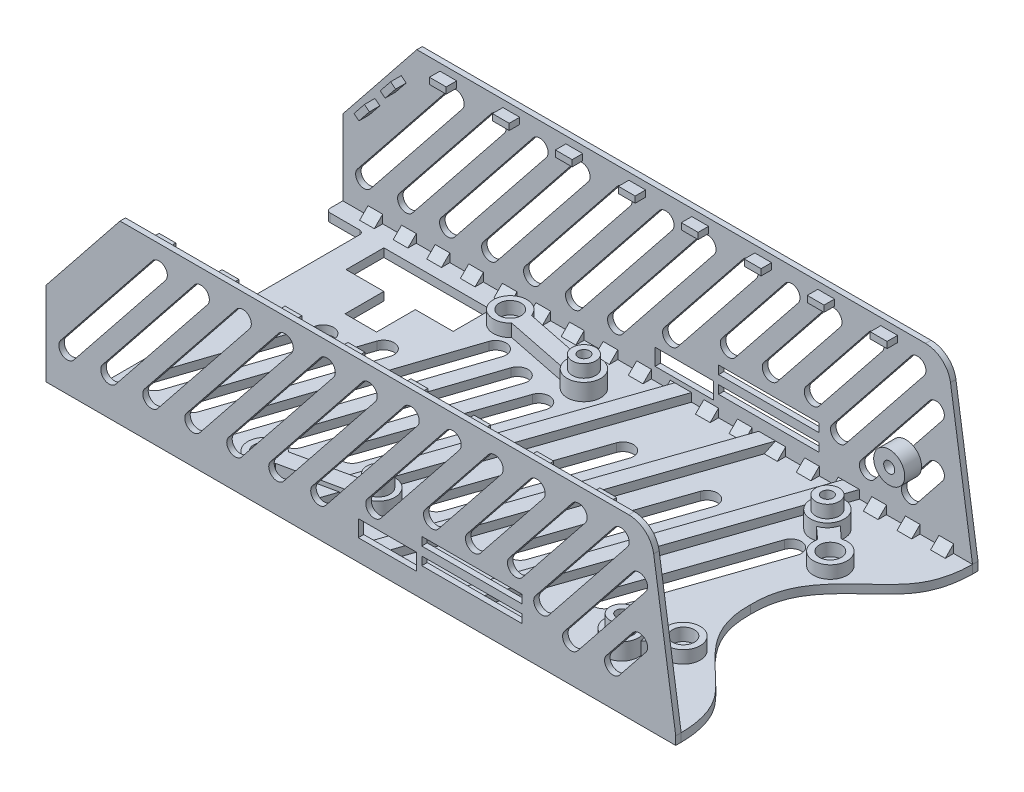
SolidWorks part; units mm, degrees
ref_plane "前视基准面" through (0, 0, 0) normal (0, 0, 1) x (1, 0, 0)
ref_plane "上视基准面" through (0, 0, 0) normal (0, 1, 0) x (1, 0, 0)
ref_plane "右视基准面" through (0, 0, 0) normal (1, 0, 0) x (0, 0, -1)
sketch "草图1" plane through (0, 0, 0) normal (0, 1, 0) x (1, 0, 0)
  line L1 (-38.5883, 74.1339) -> (111.4117, 74.1339)
  line L2 (-38.5883, 74.1339) -> (-38.5883, 2.1339)
  line L3 (-38.5883, 2.1339) -> (111.4117, 2.1339)
  line L4 (111.4117, 74.1339) -> (111.4117, 2.1339)
  dimension "D1" = 72
  dimension "D2" = 150
extrude "底板" add sketch "草图1" against normal blind 2 contours L2 L1 L4 L3
sketch "草图2" plane through (0, 0, 0) normal (0, 1, 0) x (1, 0, 0)
  circle A3 centre (28.7548, 13.929) radius 4
  circle A4 centre (86.7548, 13.929) radius 4
  circle A5 centre (86.7548, 62.929) radius 4
  circle A6 centre (28.7548, 62.929) radius 4
  dimension "D1" = 2
  dimension "D2" = 2
extrude "板卡固定柱" add sketch "草图2" along normal blind 7
sketch "螺母孔" plane through (0, -2, 0) normal (0, -1, 0) x (1, 0, 0)
  line L0 (88.7852, -11.7174) -> (85.8547, -11.0649)
  line L1 (30.7852, -11.7174) -> (27.8547, -11.0649)
  line L2 (27.8547, -11.0649) -> (25.8244, -13.2765)
  line L3 (25.8244, -13.2765) -> (26.7245, -16.1406)
  line L4 (26.7245, -16.1406) -> (29.655, -16.7931)
  line L5 (29.655, -16.7931) -> (31.6853, -14.5815)
  line L6 (31.6853, -14.5815) -> (30.7852, -11.7174)
  line L7 (85.8547, -11.0649) -> (83.8244, -13.2765)
  line L8 (83.8244, -13.2765) -> (84.7245, -16.1406)
  line L9 (84.7245, -16.1406) -> (87.655, -16.7931)
  line L10 (87.655, -16.7931) -> (89.6853, -14.5815)
  line L11 (89.6853, -14.5815) -> (88.7852, -11.7174)
  line L12 (88.7852, -60.7174) -> (85.8547, -60.0649)
  line L13 (85.8547, -60.0649) -> (83.8244, -62.2765)
  line L14 (83.8244, -62.2765) -> (84.7245, -65.1406)
  line L15 (84.7245, -65.1406) -> (87.655, -65.7931)
  line L16 (87.655, -65.7931) -> (89.6853, -63.5815)
  line L17 (89.6853, -63.5815) -> (88.7852, -60.7174)
  line L18 (30.7852, -60.7174) -> (27.8547, -60.0649)
  line L19 (27.8547, -60.0649) -> (25.8244, -62.2765)
  line L20 (25.8244, -62.2765) -> (26.7245, -65.1406)
  line L21 (26.7245, -65.1406) -> (29.655, -65.7931)
  line L22 (29.655, -65.7931) -> (31.6853, -63.5815)
  line L23 (31.6853, -63.5815) -> (30.7852, -60.7174)
  circle A0 centre (28.7548, -13.929) radius 2.6 construction
  circle A1 centre (28.7548, -13.929) radius 4 construction
  circle A2 centre (86.7548, -13.929) radius 2.6 construction
  circle A3 centre (86.7548, -62.929) radius 2.6 construction
  circle A4 centre (28.7548, -62.929) radius 2.6 construction
  dimension "D1" = 2
  dimension "D2" = 2
extrude "m2.5螺母孔槽" cut sketch "螺母孔" against normal blind 5
sketch "草图4" plane through (0, 3, 0) normal (0, -1, 0) x (1, 0, 0)
  circle A0 centre (28.7548, -13.929) radius 1.35
  circle A1 centre (28.7548, -13.929) radius 4 construction
  circle A2 centre (86.7548, -13.929) radius 1.35
  circle A3 centre (86.7548, -62.929) radius 1.35
  circle A4 centre (28.7548, -62.929) radius 1.35
  dimension "D1" = 2
  dimension "D2" = 2
extrude "m2.5通孔" cut sketch "草图4" against normal up to next
sketch "草图6" plane through (0, 7, 0) normal (0, 1, 0) x (1, 0, 0)
  circle A0 centre (28.7548, 13.929) radius 4
  circle A1 centre (28.7548, 13.929) radius 2.7944
  circle A2 centre (86.7548, 13.929) radius 4
  circle A3 centre (86.7548, 13.929) radius 2.7944
  circle A4 centre (86.7548, 62.929) radius 4
  circle A5 centre (86.7548, 62.929) radius 2.7944
  circle A6 centre (28.7548, 62.929) radius 4
  circle A7 centre (28.7548, 62.929) radius 2.7944
  dimension "D1" = 2
  dimension "D2" = 2
extrude "切除-拉伸3" cut sketch "草图6" against normal blind 3
sketch "侧边" plane through (0, 0, -74.1339) normal (0, 0, -1) x (-1, 0, 0)
  line L0 (-74.7943, 6.8381) -> (-50.9153, 6.8381)
  line L1 (-111.4117, 0) -> (38.5883, 0)
  line L6 (-74.7943, 10.8959) -> (-50.9153, 10.8959)
  line L8 (-74.7943, 10.8959) -> (-74.7943, 8.8959)
  line L9 (-74.7943, 4.8381) -> (-50.9153, 4.8381)
  line L10 (-50.9153, 4.8381) -> (-50.9153, 6.8381)
  line L11 (-74.7943, 8.8959) -> (-50.9153, 8.8959)
  line L12 (-74.7943, 6.8381) -> (-74.7943, 4.8381)
  line L13 (-50.9153, 8.8959) -> (-50.9153, 10.8959)
  line L16 (-49.6686, 3.0554) -> (-35.7948, 3.0554)
  line L17 (-35.7948, 3.0554) -> (-35.7948, 7)
  line L18 (-35.7948, 7) -> (-49.6686, 7)
  line L19 (-49.6686, 7) -> (-49.6686, 3.0554)
  line L20 (-88.7547, 7) -> (-26.2547, 7) construction
  line L21 (38.5883, -2) -> (38.5883, 0) construction
  line L22 (20.9589, 40) -> (-100.2254, 40)
  line L23 (-106.1585, 34.8932) -> (-111.4117, 0)
  line L25 (38.5883, 0) -> (38.5883, 17.9447)
  line L26 (38.5883, 17.9447) -> (20.9589, 40)
  line L27 (33.5375, 7.0719) -> (11.6845, 34.4113) construction
  line L28 (31.9753, 5.8231) -> (10.1222, 33.1625)
  line L29 (35.0998, 8.3206) -> (13.2467, 35.66)
  line L30 (23.5375, 7.0719) -> (1.6845, 34.4113) construction
  line L31 (21.9753, 5.8231) -> (0.1222, 33.1625)
  line L32 (25.0998, 8.3206) -> (3.2467, 35.66)
  line L33 (13.5375, 7.0719) -> (-8.3155, 34.4113) construction
  line L34 (11.9753, 5.8231) -> (-9.8778, 33.1625)
  line L35 (15.0998, 8.3206) -> (-6.7533, 35.66)
  line L36 (3.5375, 7.0719) -> (-18.3155, 34.4113) construction
  line L37 (1.9753, 5.8231) -> (-19.8778, 33.1625)
  line L38 (5.0998, 8.3206) -> (-16.7533, 35.66)
  line L39 (-6.4625, 7.0719) -> (-28.3155, 34.4113) construction
  line L40 (-8.0247, 5.8231) -> (-29.8778, 33.1625)
  line L41 (-4.9002, 8.3206) -> (-26.7533, 35.66)
  line L42 (-16.4625, 7.0719) -> (-38.3155, 34.4113) construction
  line L43 (-18.0247, 5.8231) -> (-39.8778, 33.1625)
  line L44 (-14.9002, 8.3206) -> (-36.7533, 35.66)
  line L45 (-26.4625, 7.0719) -> (-48.3155, 34.4113) construction
  line L46 (-28.0247, 5.8231) -> (-49.8778, 33.1625)
  line L47 (-24.9002, 8.3206) -> (-46.7533, 35.66)
  line L48 (-39.5843, 10.9775) -> (-58.3155, 34.4113) construction
  line L49 (-41.1466, 9.7287) -> (-59.8778, 33.1625)
  line L50 (-38.0221, 12.2262) -> (-56.7533, 35.66)
  line L51 (-53.3306, 15.6642) -> (-68.3155, 34.4113) construction
  line L52 (-54.8928, 14.4155) -> (-69.8778, 33.1625)
  line L53 (-51.7683, 16.913) -> (-66.7533, 35.66)
  line L54 (-63.3306, 15.6642) -> (-78.3155, 34.4113) construction
  line L55 (-64.8928, 14.4155) -> (-79.8778, 33.1625)
  line L56 (-61.7683, 16.913) -> (-76.7533, 35.66)
  line L57 (-73.3306, 15.6642) -> (-88.3155, 34.4113) construction
  line L58 (-74.8928, 14.4155) -> (-89.8778, 33.1625)
  line L59 (-71.7683, 16.913) -> (-86.7533, 35.66)
  line L60 (-79.5843, 10.9775) -> (-98.3155, 34.4113) construction
  line L61 (-81.1466, 9.7287) -> (-99.8778, 33.1625)
  line L62 (-78.0221, 12.2262) -> (-96.7533, 35.66)
  line L63 (-86.4625, 7.0719) -> (-102.6962, 27.3811) construction
  line L64 (-88.0247, 5.8231) -> (-104.2584, 26.1324)
  line L65 (-84.9002, 8.3206) -> (-101.1339, 28.6299)
  line L66 (-96.4625, 7.0719) -> (-102.7062, 14.8831) construction
  line L67 (-98.0247, 5.8231) -> (-104.2685, 13.6344)
  line L68 (-94.9002, 8.3206) -> (-101.144, 16.1319)
  arc A0 (-100.2254, 40) -> (-106.1585, 34.8932) centre (-100.2254, 34) ccw
  arc A1 (31.9753, 5.8231) -> (35.0998, 8.3206) centre (33.5375, 7.0719) ccw
  arc A2 (13.2467, 35.66) -> (10.1222, 33.1625) centre (11.6845, 34.4113) ccw
  arc A3 (21.9753, 5.8231) -> (25.0998, 8.3206) centre (23.5375, 7.0719) ccw
  arc A4 (3.2467, 35.66) -> (0.1222, 33.1625) centre (1.6845, 34.4113) ccw
  arc A5 (11.9753, 5.8231) -> (15.0998, 8.3206) centre (13.5375, 7.0719) ccw
  arc A6 (-6.7533, 35.66) -> (-9.8778, 33.1625) centre (-8.3155, 34.4113) ccw
  arc A7 (1.9753, 5.8231) -> (5.0998, 8.3206) centre (3.5375, 7.0719) ccw
  arc A8 (-16.7533, 35.66) -> (-19.8778, 33.1625) centre (-18.3155, 34.4113) ccw
  arc A9 (-8.0247, 5.8231) -> (-4.9002, 8.3206) centre (-6.4625, 7.0719) ccw
  arc A10 (-26.7533, 35.66) -> (-29.8778, 33.1625) centre (-28.3155, 34.4113) ccw
  arc A11 (-18.0247, 5.8231) -> (-14.9002, 8.3206) centre (-16.4625, 7.0719) ccw
  arc A12 (-36.7533, 35.66) -> (-39.8778, 33.1625) centre (-38.3155, 34.4113) ccw
  arc A13 (-28.0247, 5.8231) -> (-24.9002, 8.3206) centre (-26.4625, 7.0719) ccw
  arc A14 (-46.7533, 35.66) -> (-49.8778, 33.1625) centre (-48.3155, 34.4113) ccw
  arc A15 (-41.1466, 9.7287) -> (-38.0221, 12.2262) centre (-39.5843, 10.9775) ccw
  arc A16 (-56.7533, 35.66) -> (-59.8778, 33.1625) centre (-58.3155, 34.4113) ccw
  arc A17 (-54.8928, 14.4155) -> (-51.7683, 16.913) centre (-53.3306, 15.6642) ccw
  arc A18 (-66.7533, 35.66) -> (-69.8778, 33.1625) centre (-68.3155, 34.4113) ccw
  arc A19 (-64.8928, 14.4155) -> (-61.7683, 16.913) centre (-63.3306, 15.6642) ccw
  arc A20 (-76.7533, 35.66) -> (-79.8778, 33.1625) centre (-78.3155, 34.4113) ccw
  arc A21 (-74.8928, 14.4155) -> (-71.7683, 16.913) centre (-73.3306, 15.6642) ccw
  arc A22 (-86.7533, 35.66) -> (-89.8778, 33.1625) centre (-88.3155, 34.4113) ccw
  arc A23 (-81.1466, 9.7287) -> (-78.0221, 12.2262) centre (-79.5843, 10.9775) ccw
  arc A24 (-96.7533, 35.66) -> (-99.8778, 33.1625) centre (-98.3155, 34.4113) ccw
  arc A25 (-88.0247, 5.8231) -> (-84.9002, 8.3206) centre (-86.4625, 7.0719) ccw
  arc A26 (-101.1339, 28.6299) -> (-104.2584, 26.1324) centre (-102.6962, 27.3811) ccw
  arc A27 (-98.0247, 5.8231) -> (-94.9002, 8.3206) centre (-96.4625, 7.0719) ccw
  arc A28 (-101.144, 16.1319) -> (-104.2685, 13.6344) centre (-102.7062, 14.8831) ccw
  point P2 (22.611, 20.7416)
  point P31 (12.611, 20.7416)
  point P38 (2.611, 20.7416)
  point P48 (-7.389, 20.7416)
  point P55 (-17.389, 20.7416)
  point P62 (-27.389, 20.7416)
  point P69 (-37.389, 20.7416)
  point P76 (-48.9499, 22.6944)
  point P83 (-60.8231, 25.0378)
  point P90 (-70.8231, 25.0378)
  point P97 (-80.8231, 25.0378)
  point P104 (-88.9499, 22.6944)
  point P111 (-94.5793, 17.2265)
  point P118 (-99.5843, 10.9775)
  dimension "D1" = 6
  dimension "D2" = 40
extrude "侧边凸台" add sketch "侧边" against normal blind 1.3
sketch "草图14" plane through (0, 0, -72.8339) normal (0, 0, 1) x (1, 0, 0)
  line L0 (-30.9262, 24.9677) -> (-33.4237, 21.8432)
  line L1 (-33.4237, 21.8432) -> (-32.2521, 20.9067)
  line L2 (-24.6825, 32.779) -> (-27.18, 29.6545)
  line L3 (-27.18, 29.6545) -> (-26.0083, 28.7179)
  line L4 (-26.0083, 28.7179) -> (-23.5108, 31.8424)
  line L5 (-23.5108, 31.8424) -> (-24.6825, 32.779)
  line L6 (-32.2521, 20.9067) -> (-29.7546, 24.0312)
  line L7 (-29.7546, 24.0312) -> (-30.9262, 24.9677)
  line L9 (-15.4544, 38.32) -> (-11.4544, 38.32)
  line L10 (-11.4544, 38.32) -> (-11.4544, 36.82)
  line L11 (-11.4544, 36.82) -> (-15.4544, 36.82)
  line L12 (-15.4544, 36.82) -> (-15.4544, 38.32)
  line L13 (-20.9589, 40) -> (100.2254, 40) construction
  line L14 (-0.4544, 38.32) -> (3.5456, 38.32)
  line L15 (3.5456, 38.32) -> (3.5456, 36.82)
  line L16 (3.5456, 36.82) -> (-0.4544, 36.82)
  line L17 (-0.4544, 36.82) -> (-0.4544, 38.32)
  line L18 (14.5456, 38.32) -> (18.5456, 38.32)
  line L19 (18.5456, 38.32) -> (18.5456, 36.82)
  line L20 (18.5456, 36.82) -> (14.5456, 36.82)
  line L21 (14.5456, 36.82) -> (14.5456, 38.32)
  line L22 (29.5456, 38.32) -> (33.5456, 38.32)
  line L23 (33.5456, 38.32) -> (33.5456, 36.82)
  line L24 (33.5456, 36.82) -> (29.5456, 36.82)
  line L25 (29.5456, 36.82) -> (29.5456, 38.32)
  line L26 (44.5456, 38.32) -> (48.5456, 38.32)
  line L27 (48.5456, 38.32) -> (48.5456, 36.82)
  line L28 (48.5456, 36.82) -> (44.5456, 36.82)
  line L29 (44.5456, 36.82) -> (44.5456, 38.32)
  line L30 (59.5456, 38.32) -> (63.5456, 38.32)
  line L31 (63.5456, 38.32) -> (63.5456, 36.82)
  line L32 (63.5456, 36.82) -> (59.5456, 36.82)
  line L33 (59.5456, 36.82) -> (59.5456, 38.32)
  line L34 (74.5456, 38.32) -> (78.5456, 38.32)
  line L35 (78.5456, 38.32) -> (78.5456, 36.82)
  line L36 (78.5456, 36.82) -> (74.5456, 36.82)
  line L37 (74.5456, 36.82) -> (74.5456, 38.32)
  line L38 (89.5456, 38.32) -> (93.5456, 38.32)
  line L39 (93.5456, 38.32) -> (93.5456, 36.82)
  line L40 (93.5456, 36.82) -> (89.5456, 36.82)
  line L41 (89.5456, 36.82) -> (89.5456, 38.32)
  dimension "D1" = 2
  dimension "D2" = 1.68
  dimension "D3" = 1.5
  dimension "D4" = 4
  dimension "D5" = 8
extrude "顶盖支架" add sketch "草图14" along normal blind 2.5
sketch "草图15" plane through (0, -2, 0) normal (0, -1, 0) x (1, 0, 0)
  line L0 (-38.5883, -38.1339) -> (111.4117, -38.1339)
  line L1 (-38.5883, -74.1339) -> (-38.5883, -2.1339) construction
  line L2 (111.4117, -74.1339) -> (111.4117, -2.1339) construction
ref_plane "基准面7" through (0, 0, -38.1339) normal (0, 0, -1) x (-1, 0, 0)
mirror "镜向1" about plane through (0, 0, -38.1339) normal (0, 0, -1) of "侧边凸台", "顶盖支架"
sketch "草图17" plane through (0, -2, 0) normal (0, -1, 0) x (1, 0, 0)
  line L0 (-7.5175, -59.0417) -> (1.4825, -59.0417)
  line L1 (1.4825, -59.0417) -> (1.4825, -68.0417)
  line L6 (1.4825, -68.0417) -> (-24.0175, -68.0417)
  line L7 (-24.0175, -68.0417) -> (-24.0175, -59.0417)
  line L8 (-24.0175, -59.0417) -> (-15.0175, -59.0417)
  line L9 (6.7325, -8.8917) -> (6.7325, -67.3917)
  line L10 (6.7325, -67.3917) -> (6.7325, -38.1417)
  line L11 (-7.5175, -49.7917) -> (-15.0175, -49.7917)
  line L12 (-7.5175, -59.0417) -> (-7.5175, -49.7917)
  line L14 (-15.0175, -49.7917) -> (-15.0175, -59.0417)
  line L15 (6.7325, -38.1417) -> (17.9206, -38.1417)
  circle A6 centre (6.7325, -67.3917) radius 1.55
  circle A7 centre (94.7325, -55.6417) radius 1.55
  circle A8 centre (6.7325, -67.3917) radius 1.55
  circle A9 centre (94.7325, -20.6417) radius 1.55
  circle A10 centre (6.7325, -8.8917) radius 1.55
  dimension "D1" = 9
  dimension "D2" = 9
  dimension "D3" = 9
  dimension "D4" = 58.5
extrude "链接孔" cut sketch "草图17" against normal blind 2.5 contours A6 | L11 L14 L12 | A7 | A9 | A10 region at (-11.2675, -2, -61.4236) region at (7.7975, -2, -66.3267)
sketch "草图18" plane through (0, 0, 0) normal (0, 1, 0) x (1, 0, 0)
  line L0 (-38.5883, 7.4339) -> (-38.5883, 68.8339)
  line L13 (-23.5883, 13.0192) -> (-13.5883, 43.1339) construction
  line L14 (23.1, 38.1339) -> (-23.1, 38.1339) construction
  line L15 (-25.9609, 13.8071) -> (-15.9609, 43.9218)
  line L22 (-21.2157, 12.2314) -> (-11.2157, 42.3461)
  line L23 (-38.5883, 7.4339) -> (-30.5883, 7.4339)
  line L24 (-29.5883, 8.4339) -> (-29.5883, 67.8339)
  line L25 (-30.5883, 68.8339) -> (-38.5883, 68.8339)
  line L26 (-38.5883, 38.1339) -> (111.4117, 38.1339) construction
  line L27 (-14.5883, 13.0192) -> (-3.2431, 47.1848) construction
  line L28 (-16.9609, 13.8071) -> (-5.6157, 47.9727)
  line L29 (-12.2157, 12.2314) -> (-0.8705, 46.3969)
  line L30 (-5.5883, 13.0192) -> (10.1689, 60.4714) construction
  line L31 (-7.9609, 13.8071) -> (7.7963, 61.2593)
  line L32 (-3.2157, 12.2314) -> (12.5415, 59.6836)
  line L33 (4.9874, 17.7644) -> (18.2234, 57.6243) construction
  line L34 (2.6148, 18.5523) -> (15.8508, 58.4121)
  line L35 (7.36, 16.9766) -> (20.596, 56.8364)
  line L36 (14.9242, 21.5786) -> (26.2679, 54.6893) construction
  line L37 (12.5591, 22.3889) -> (23.9029, 55.4996)
  line L38 (17.2892, 20.7683) -> (28.633, 53.879)
  line L39 (111.4117, 72.8339) -> (-38.5883, 72.8339) construction
  line L41 (111.4117, 72.8339) -> (111.4117, 3.4339)
  line L44 (34.9242, 21.5786) -> (46.2679, 54.6893) construction
  line L45 (32.5591, 22.3889) -> (43.9029, 55.4996)
  line L46 (37.2892, 20.7683) -> (48.633, 53.879)
  line L50 (54.9242, 21.5786) -> (66.2679, 54.6893) construction
  line L51 (52.5591, 22.3889) -> (63.9029, 55.4996)
  line L52 (57.2892, 20.7683) -> (68.633, 53.879)
  line L56 (74.9242, 21.5786) -> (86.2679, 54.6893) construction
  line L57 (72.5591, 22.3889) -> (83.9029, 55.4996)
  line L58 (77.2892, 20.7683) -> (88.633, 53.879)
  line L84 (44.9242, 21.5786) -> (56.2679, 54.6893) construction
  line L85 (42.5591, 22.3889) -> (53.9029, 55.4996)
  line L86 (47.2892, 20.7683) -> (58.633, 53.879)
  line L87 (64.9242, 21.5786) -> (76.2679, 54.6893) construction
  line L88 (62.5591, 22.3889) -> (73.9029, 55.4996)
  line L89 (67.2892, 20.7683) -> (78.633, 53.879)
  line L90 (24.9242, 21.5786) -> (36.2679, 54.6893) construction
  line L91 (22.5591, 22.3889) -> (33.9029, 55.4996)
  line L92 (27.2892, 20.7683) -> (38.633, 53.879)
  line L93 (44.9242, 21.5786) -> (56.2679, 54.6893) construction
  line L94 (42.5591, 22.3889) -> (53.9029, 55.4996)
  line L95 (47.2892, 20.7683) -> (58.633, 53.879)
  line L96 (64.9242, 21.5786) -> (76.2679, 54.6893) construction
  line L97 (62.5591, 22.3889) -> (73.9029, 55.4996)
  line L98 (67.2892, 20.7683) -> (78.633, 53.879)
  line L99 (24.9242, 21.5786) -> (36.2679, 54.6893) construction
  line L100 (22.5591, 22.3889) -> (33.9029, 55.4996)
  line L101 (27.2892, 20.7683) -> (38.633, 53.879)
  arc A2 (-25.9609, 13.8071) -> (-21.2157, 12.2314) centre (-23.5883, 13.0192) ccw
  arc A3 (-11.2157, 42.3461) -> (-15.9609, 43.9218) centre (-13.5883, 43.1339) ccw
  arc A4 (-16.9609, 13.8071) -> (-12.2157, 12.2314) centre (-14.5883, 13.0192) ccw
  arc A5 (-0.8705, 46.3969) -> (-5.6157, 47.9727) centre (-3.2431, 47.1848) ccw
  arc A6 (-7.9609, 13.8071) -> (-3.2157, 12.2314) centre (-5.5883, 13.0192) ccw
  arc A7 (12.5415, 59.6836) -> (7.7963, 61.2593) centre (10.1689, 60.4714) ccw
  arc A8 (2.6148, 18.5523) -> (7.36, 16.9766) centre (4.9874, 17.7644) ccw
  arc A9 (20.596, 56.8364) -> (15.8508, 58.4121) centre (18.2234, 57.6243) ccw
  arc A10 (12.5591, 22.3889) -> (17.2892, 20.7683) centre (14.9242, 21.5786) ccw
  arc A11 (28.633, 53.879) -> (23.9029, 55.4996) centre (26.2679, 54.6893) ccw
  arc A18 (-30.5883, 7.4339) -> (-29.5883, 8.4339) centre (-30.5883, 8.4339) ccw
  arc A19 (-29.5883, 67.8339) -> (-30.5883, 68.8339) centre (-30.5883, 67.8339) ccw
  arc A21 (32.5591, 22.3889) -> (37.2892, 20.7683) centre (34.9242, 21.5786) ccw
  arc A22 (48.633, 53.879) -> (43.9029, 55.4996) centre (46.2679, 54.6893) ccw
  arc A25 (52.5591, 22.3889) -> (57.2892, 20.7683) centre (54.9242, 21.5786) ccw
  arc A26 (68.633, 53.879) -> (63.9029, 55.4996) centre (66.2679, 54.6893) ccw
  arc A29 (72.5591, 22.3889) -> (77.2892, 20.7683) centre (74.9242, 21.5786) ccw
  arc A30 (88.633, 53.879) -> (83.9029, 55.4996) centre (86.2679, 54.6893) ccw
  arc A54 (42.5591, 22.3889) -> (47.2892, 20.7683) centre (44.9242, 21.5786) ccw
  arc A55 (58.633, 53.879) -> (53.9029, 55.4996) centre (56.2679, 54.6893) ccw
  arc A56 (62.5591, 22.3889) -> (67.2892, 20.7683) centre (64.9242, 21.5786) ccw
  arc A57 (78.633, 53.879) -> (73.9029, 55.4996) centre (76.2679, 54.6893) ccw
  arc A58 (22.5591, 22.3889) -> (27.2892, 20.7683) centre (24.9242, 21.5786) ccw
  arc A59 (38.633, 53.879) -> (33.9029, 55.4996) centre (36.2679, 54.6893) ccw
  spline S0 degree 3 poles (111.4117, 72.8339) (111.3592, 67.7048) (109.517, 62.8559) (100.4801, 53.3454) (93.0189, 48.3908) (93.2722, 38.1339) knots 0 0 0 0 0.239028 0.339028 1 1 1 1
  spline S1 degree 3 poles (111.4117, 3.4339) (111.3592, 8.5631) (109.517, 13.412) (100.4801, 22.9225) (93.0189, 27.8771) (93.2722, 38.1339) knots 0 0 0 0 0.239028 0.339028 1 1 1 1
  point P6 (50.596, 38.1339)
  point P20 (-18.5883, 28.0766)
  point P31 (-8.9157, 30.102)
  point P38 (2.2903, 36.7453)
  point P44 (40.596, 38.1339)
  point P47 (11.6054, 37.6944)
  point P54 (20.596, 38.1339)
  point P65 (30.596, 38.1339)
  point P68 (28.7548, 38.1339)
  point P72 (70.596, 38.1339)
  point P82 (-29.5883, 7.4339)
  point P87 (60.596, 38.1339)
  point P101 (80.596, 38.1339)
  point P109 (50.596, 38.1339)
  point P116 (70.596, 38.1339)
  point P123 (30.596, 38.1339)
  point P130 (50.596, 38.1339)
  point P137 (70.596, 38.1339)
  point P144 (30.596, 38.1339)
  point P151 (50.596, 38.1339)
  point P158 (70.596, 38.1339)
  point P165 (30.596, 38.1339)
  point P172 (50.596, 38.1339)
  point P179 (70.596, 38.1339)
  point P186 (30.596, 38.1339)
  dimension "D8" = 2.5
  dimension "D1" = 0
  dimension "D2" = 7
  dimension "D6" = 9
  dimension "D7" = 6
  dimension "D9" = 5
  dimension "D10" = 16
  dimension "D11" = 12.3625
extrude "切除-拉伸6" cut sketch "草图18" against normal up to next
fillet "圆角3" radius 1 2 edges at (-38.5883, -1, -7.4339) (-38.5883, -1, -68.8339)
sketch "草图21" plane through (0, 0, 0) normal (0, 1, 0) x (1, 0, 0)
  line L19 (24.9625, 61.6568) -> (9.7304, 64.7436)
  line L21 (25.757, 65.5771) -> (10.5248, 68.6639)
  line L24 (24.9468, 14.8691) -> (9.6967, 11.5776)
  line L26 (25.7907, 10.9592) -> (10.5406, 7.6676)
  line L32 (90.7942, 19.9417) -> (88.1178, 17.6896)
  line L33 (93.3696, 16.8811) -> (90.6931, 14.629)
  line L36 (87.9636, 59.116) -> (90.826, 56.5014)
  line L38 (90.6614, 62.0693) -> (93.5237, 59.4547)
  arc A12 (10.5248, 68.6639) -> (9.7304, 64.7436) centre (6.7325, 67.3917) ccw
  circle A13 centre (6.7325, 67.3917) radius 2.6
  arc A14 (25.757, 65.5771) -> (24.9625, 61.6568) centre (28.7548, 62.929) ccw
  arc A15 (9.6967, 11.5776) -> (10.5406, 7.6676) centre (6.7325, 8.8917) ccw
  circle A16 centre (6.7325, 8.8917) radius 2.6
  arc A17 (24.9468, 14.8691) -> (25.7907, 10.9592) centre (28.7548, 13.645) ccw
  arc A18 (93.3696, 16.8811) -> (90.7942, 19.9417) centre (94.7325, 20.6417) ccw
  circle A19 centre (94.7325, 20.6417) radius 2.6
  arc A20 (90.6931, 14.629) -> (88.1178, 17.6896) centre (86.7548, 13.929) ccw
  arc A21 (90.826, 56.5014) -> (93.5237, 59.4547) centre (94.7325, 55.6417) ccw
  circle A22 centre (94.7325, 55.6417) radius 2.6
  arc A23 (87.9636, 59.116) -> (90.6614, 62.0693) centre (86.7548, 62.929) ccw
extrude "板卡固定加强筋" add sketch "草图21" along normal blind 3
sketch "草图23" plane through (0, 0, 0) normal (0, 1, 0) x (1, 0, 0)
  line L0 (111.4117, 72.8339) -> (-38.5883, 72.8339) construction
  line L1 (-32.5883, 72.8339) -> (-29.0883, 72.8339)
  line L2 (-32.5883, 72.8339) -> (-32.5883, 70.8339)
  line L3 (-32.5883, 70.8339) -> (-29.0883, 70.8339)
  line L4 (-29.0883, 72.8339) -> (-29.0883, 70.8339)
  line L5 (-24.5883, 72.8339) -> (-24.5883, 70.8339)
  line L6 (-24.5883, 72.8339) -> (-21.0883, 72.8339)
  line L7 (-24.5883, 70.8339) -> (-21.0883, 70.8339)
  line L8 (-21.0883, 72.8339) -> (-21.0883, 70.8339)
  line L9 (-16.5883, 72.8339) -> (-16.5883, 70.8339)
  line L10 (-16.5883, 72.8339) -> (-13.0883, 72.8339)
  line L11 (-16.5883, 70.8339) -> (-13.0883, 70.8339)
  line L12 (-13.0883, 72.8339) -> (-13.0883, 70.8339)
  line L13 (-8.5883, 72.8339) -> (-8.5883, 70.8339)
  line L14 (-8.5883, 72.8339) -> (-5.0883, 72.8339)
  line L15 (-8.5883, 70.8339) -> (-5.0883, 70.8339)
  line L16 (-5.0883, 72.8339) -> (-5.0883, 70.8339)
  line L17 (-0.5883, 72.8339) -> (-0.5883, 70.8339)
  line L18 (-0.5883, 72.8339) -> (2.9117, 72.8339)
  line L19 (-0.5883, 70.8339) -> (2.9117, 70.8339)
  line L20 (2.9117, 72.8339) -> (2.9117, 70.8339)
  line L21 (7.4117, 72.8339) -> (7.4117, 70.8339)
  line L22 (7.4117, 72.8339) -> (10.9117, 72.8339)
  line L23 (7.4117, 70.8339) -> (10.9117, 70.8339)
  line L24 (10.9117, 72.8339) -> (10.9117, 70.8339)
  line L25 (15.4117, 72.8339) -> (15.4117, 70.8339)
  line L26 (15.4117, 72.8339) -> (18.9117, 72.8339)
  line L27 (15.4117, 70.8339) -> (18.9117, 70.8339)
  line L28 (18.9117, 72.8339) -> (18.9117, 70.8339)
  line L29 (23.4117, 72.8339) -> (23.4117, 70.8339)
  line L30 (23.4117, 72.8339) -> (26.9117, 72.8339)
  line L31 (23.4117, 70.8339) -> (26.9117, 70.8339)
  line L32 (26.9117, 72.8339) -> (26.9117, 70.8339)
  line L33 (31.4117, 72.8339) -> (31.4117, 70.8339)
  line L34 (31.4117, 72.8339) -> (34.9117, 72.8339)
  line L35 (31.4117, 70.8339) -> (34.9117, 70.8339)
  line L36 (34.9117, 72.8339) -> (34.9117, 70.8339)
  line L37 (39.4117, 72.8339) -> (39.4117, 70.8339)
  line L38 (39.4117, 72.8339) -> (42.9117, 72.8339)
  line L39 (39.4117, 70.8339) -> (42.9117, 70.8339)
  line L40 (42.9117, 72.8339) -> (42.9117, 70.8339)
  line L41 (47.4117, 72.8339) -> (47.4117, 70.8339)
  line L42 (47.4117, 72.8339) -> (50.9117, 72.8339)
  line L43 (47.4117, 70.8339) -> (50.9117, 70.8339)
  line L44 (50.9117, 72.8339) -> (50.9117, 70.8339)
  line L45 (55.4117, 72.8339) -> (55.4117, 70.8339)
  line L46 (55.4117, 72.8339) -> (58.9117, 72.8339)
  line L47 (55.4117, 70.8339) -> (58.9117, 70.8339)
  line L48 (58.9117, 72.8339) -> (58.9117, 70.8339)
  line L49 (63.4117, 72.8339) -> (63.4117, 70.8339)
  line L50 (63.4117, 72.8339) -> (66.9117, 72.8339)
  line L51 (63.4117, 70.8339) -> (66.9117, 70.8339)
  line L52 (66.9117, 72.8339) -> (66.9117, 70.8339)
  line L53 (71.4117, 72.8339) -> (71.4117, 70.8339)
  line L54 (71.4117, 72.8339) -> (74.9117, 72.8339)
  line L55 (71.4117, 70.8339) -> (74.9117, 70.8339)
  line L56 (74.9117, 72.8339) -> (74.9117, 70.8339)
  line L57 (79.4117, 72.8339) -> (79.4117, 70.8339)
  line L58 (79.4117, 72.8339) -> (82.9117, 72.8339)
  line L59 (79.4117, 70.8339) -> (82.9117, 70.8339)
  line L60 (82.9117, 72.8339) -> (82.9117, 70.8339)
  line L61 (87.4117, 72.8339) -> (87.4117, 70.8339)
  line L62 (87.4117, 72.8339) -> (90.9117, 72.8339)
  line L63 (87.4117, 70.8339) -> (90.9117, 70.8339)
  line L64 (90.9117, 72.8339) -> (90.9117, 70.8339)
  line L65 (95.4117, 72.8339) -> (95.4117, 70.8339)
  line L66 (95.4117, 72.8339) -> (98.9117, 72.8339)
  line L67 (95.4117, 70.8339) -> (98.9117, 70.8339)
  line L68 (98.9117, 72.8339) -> (98.9117, 70.8339)
  line L69 (103.4117, 72.8339) -> (103.4117, 70.8339)
  line L70 (103.4117, 72.8339) -> (106.9117, 72.8339)
  line L71 (103.4117, 70.8339) -> (106.9117, 70.8339)
  line L72 (106.9117, 72.8339) -> (106.9117, 70.8339)
  line L73 (23.1, 38.1339) -> (-23.1, 38.1339) construction
  line L74 (106.9117, 3.4339) -> (106.9117, 5.4339)
  line L75 (103.4117, 5.4339) -> (106.9117, 5.4339)
  line L76 (103.4117, 3.4339) -> (106.9117, 3.4339)
  line L77 (103.4117, 3.4339) -> (103.4117, 5.4339)
  line L78 (98.9117, 3.4339) -> (98.9117, 5.4339)
  line L79 (95.4117, 5.4339) -> (98.9117, 5.4339)
  line L80 (95.4117, 3.4339) -> (98.9117, 3.4339)
  line L81 (95.4117, 3.4339) -> (95.4117, 5.4339)
  line L82 (90.9117, 3.4339) -> (90.9117, 5.4339)
  line L83 (87.4117, 5.4339) -> (90.9117, 5.4339)
  line L84 (87.4117, 3.4339) -> (90.9117, 3.4339)
  line L85 (87.4117, 3.4339) -> (87.4117, 5.4339)
  line L86 (82.9117, 3.4339) -> (82.9117, 5.4339)
  line L87 (79.4117, 5.4339) -> (82.9117, 5.4339)
  line L88 (79.4117, 3.4339) -> (82.9117, 3.4339)
  line L89 (79.4117, 3.4339) -> (79.4117, 5.4339)
  line L90 (74.9117, 3.4339) -> (74.9117, 5.4339)
  line L91 (71.4117, 5.4339) -> (74.9117, 5.4339)
  line L92 (71.4117, 3.4339) -> (74.9117, 3.4339)
  line L93 (71.4117, 3.4339) -> (71.4117, 5.4339)
  line L94 (66.9117, 3.4339) -> (66.9117, 5.4339)
  line L95 (63.4117, 5.4339) -> (66.9117, 5.4339)
  line L96 (63.4117, 3.4339) -> (66.9117, 3.4339)
  line L97 (63.4117, 3.4339) -> (63.4117, 5.4339)
  line L98 (58.9117, 3.4339) -> (58.9117, 5.4339)
  line L99 (55.4117, 5.4339) -> (58.9117, 5.4339)
  line L100 (55.4117, 3.4339) -> (58.9117, 3.4339)
  line L101 (55.4117, 3.4339) -> (55.4117, 5.4339)
  line L102 (50.9117, 3.4339) -> (50.9117, 5.4339)
  line L103 (47.4117, 5.4339) -> (50.9117, 5.4339)
  line L104 (47.4117, 3.4339) -> (50.9117, 3.4339)
  line L105 (47.4117, 3.4339) -> (47.4117, 5.4339)
  line L106 (42.9117, 3.4339) -> (42.9117, 5.4339)
  line L107 (39.4117, 5.4339) -> (42.9117, 5.4339)
  line L108 (39.4117, 3.4339) -> (42.9117, 3.4339)
  line L109 (39.4117, 3.4339) -> (39.4117, 5.4339)
  line L110 (34.9117, 3.4339) -> (34.9117, 5.4339)
  line L111 (31.4117, 5.4339) -> (34.9117, 5.4339)
  line L112 (31.4117, 3.4339) -> (34.9117, 3.4339)
  line L113 (31.4117, 3.4339) -> (31.4117, 5.4339)
  line L114 (26.9117, 3.4339) -> (26.9117, 5.4339)
  line L115 (23.4117, 5.4339) -> (26.9117, 5.4339)
  line L116 (23.4117, 3.4339) -> (26.9117, 3.4339)
  line L117 (23.4117, 3.4339) -> (23.4117, 5.4339)
  line L118 (18.9117, 3.4339) -> (18.9117, 5.4339)
  line L119 (15.4117, 5.4339) -> (18.9117, 5.4339)
  line L120 (15.4117, 3.4339) -> (18.9117, 3.4339)
  line L121 (15.4117, 3.4339) -> (15.4117, 5.4339)
  line L122 (10.9117, 3.4339) -> (10.9117, 5.4339)
  line L123 (7.4117, 5.4339) -> (10.9117, 5.4339)
  line L124 (7.4117, 3.4339) -> (10.9117, 3.4339)
  line L125 (7.4117, 3.4339) -> (7.4117, 5.4339)
  line L126 (2.9117, 3.4339) -> (2.9117, 5.4339)
  line L127 (-0.5883, 5.4339) -> (2.9117, 5.4339)
  line L128 (-0.5883, 3.4339) -> (2.9117, 3.4339)
  line L129 (-0.5883, 3.4339) -> (-0.5883, 5.4339)
  line L130 (-5.0883, 3.4339) -> (-5.0883, 5.4339)
  line L131 (-8.5883, 5.4339) -> (-5.0883, 5.4339)
  line L132 (-8.5883, 3.4339) -> (-5.0883, 3.4339)
  line L133 (-8.5883, 3.4339) -> (-8.5883, 5.4339)
  line L134 (-13.0883, 3.4339) -> (-13.0883, 5.4339)
  line L135 (-16.5883, 5.4339) -> (-13.0883, 5.4339)
  line L136 (-16.5883, 3.4339) -> (-13.0883, 3.4339)
  line L137 (-16.5883, 3.4339) -> (-16.5883, 5.4339)
  line L138 (-21.0883, 3.4339) -> (-21.0883, 5.4339)
  line L139 (-24.5883, 5.4339) -> (-21.0883, 5.4339)
  line L140 (-24.5883, 3.4339) -> (-21.0883, 3.4339)
  line L141 (-24.5883, 3.4339) -> (-24.5883, 5.4339)
  line L142 (-29.0883, 3.4339) -> (-29.0883, 5.4339)
  line L143 (-32.5883, 5.4339) -> (-29.0883, 5.4339)
  line L144 (-32.5883, 3.4339) -> (-32.5883, 5.4339)
  line L145 (-32.5883, 3.4339) -> (-29.0883, 3.4339)
  dimension "D1" = 6
  dimension "D2" = 3.5
  dimension "D3" = 2
  dimension "D4" = 18
extrude "凸台-拉伸7" add sketch "草图23" along normal blind 2.5
chamfer "倒角1" distance 2.5 angle 45 36 edges at (-30.8383, 2.5, -70.8339) (-22.8383, 2.5, -5.4339) (-30.8383, 2.5, -5.4339) (-14.8383, 2.5, -5.4339) (-6.8383, 2.5, -5.4339) (1.1617, 2.5, -5.4339) (9.8276, 2.5, -5.4339) (17.1617, 2.5, -5.4339) (25.1617, 2.5, -5.4339) (33.1617, 2.5, -5.4339) (41.1617, 2.5, -5.4339) (49.1617, 2.5, -5.4339) (57.1617, 2.5, -5.4339) (65.1617, 2.5, -5.4339) (73.1617, 2.5, -5.4339) (81.1617, 2.5, -5.4339) (89.1617, 2.5, -5.4339) (97.1617, 2.5, -5.4339) (105.1617, 2.5, -5.4339) (105.1617, 2.5, -70.8339) (97.1617, 2.5, -70.8339) (89.1617, 2.5, -70.8339) (81.1617, 2.5, -70.8339) (73.1617, 2.5, -70.8339) (65.1617, 2.5, -70.8339) (57.1617, 2.5, -70.8339) (49.1617, 2.5, -70.8339) (41.1617, 2.5, -70.8339) (33.1617, 2.5, -70.8339) (25.1617, 2.5, -70.8339) (17.1617, 2.5, -70.8339) (9.8408, 2.5, -70.8339) (1.1617, 2.5, -70.8339) (-6.8383, 2.5, -70.8339) (-14.8383, 2.5, -70.8339) (-22.8383, 2.5, -70.8339)
sketch "草图25" plane through (0, 0, 0) normal (0, 1, 0) x (1, 0, 0)
  line L8 (84.4843, 72.8339) -> (80.4843, 72.8339)
  line L10 (60.7078, 3.4339) -> (56.7078, 3.4339)
  line L11 (64.4843, 72.8339) -> (60.4843, 72.8339)
  line L12 (40.7078, 3.4339) -> (36.7078, 3.4339)
  line L13 (84.4843, 72.8339) -> (60.7078, 3.4339)
  line L14 (64.4843, 72.8339) -> (40.7078, 3.4339)
  line L15 (80.4843, 72.8339) -> (56.7078, 3.4339)
  line L16 (60.4843, 72.8339) -> (36.7078, 3.4339)
  line L17 (44.4843, 72.8339) -> (40.4843, 72.8339)
  line L18 (20.7078, 3.4339) -> (16.7078, 3.4339)
  line L19 (44.4843, 72.8339) -> (20.7078, 3.4339)
  line L20 (40.4843, 72.8339) -> (16.7078, 3.4339)
  dimension "D1" = 3
extrude "凸台-拉伸8" add sketch "草图25" along normal blind 2
sketch "草图10" plane through (0, 0, -72.8339) normal (0, 0, 1) x (1, 0, 0)
  circle A0 centre (95.5627, 14.116) radius 3.7
extrude "凸台-拉伸5" add sketch "草图10" along normal blind 4
sketch "草图11" plane through (0, 0, -68.8339) normal (0, 0, 1) x (1, 0, 0)
  circle A0 centre (95.5627, 14.116) radius 1.32
extrude "切除-拉伸4" cut sketch "草图11" against normal up to next
sketch "草图12" plane through (0, 0, -74.1339) normal (0, 0, -1) x (-1, 0, 0)
  circle A0 centre (-95.5627, 14.116) radius 2.5
ref_plane "基准面6" through (108.3973, -11, 54.1256) normal (-0.5878, 0, -0.809) x (-0.809, 0, 0.5878)
extrude "切除-拉伸5" cut sketch "草图12" against normal blind 3
sketch "草图8" plane through (0, 0, 0) normal (0, 1, 0) x (1, 0, 0)
  line L0 (86.7548, 62.929) -> (28.7548, 13.929)
  line L1 (28.7548, 13.929) -> (28.7548, 62.929)
  line L2 (28.7548, 62.929) -> (86.7548, 13.929)
  line L3 (86.7548, 13.929) -> (86.7548, 62.929)
